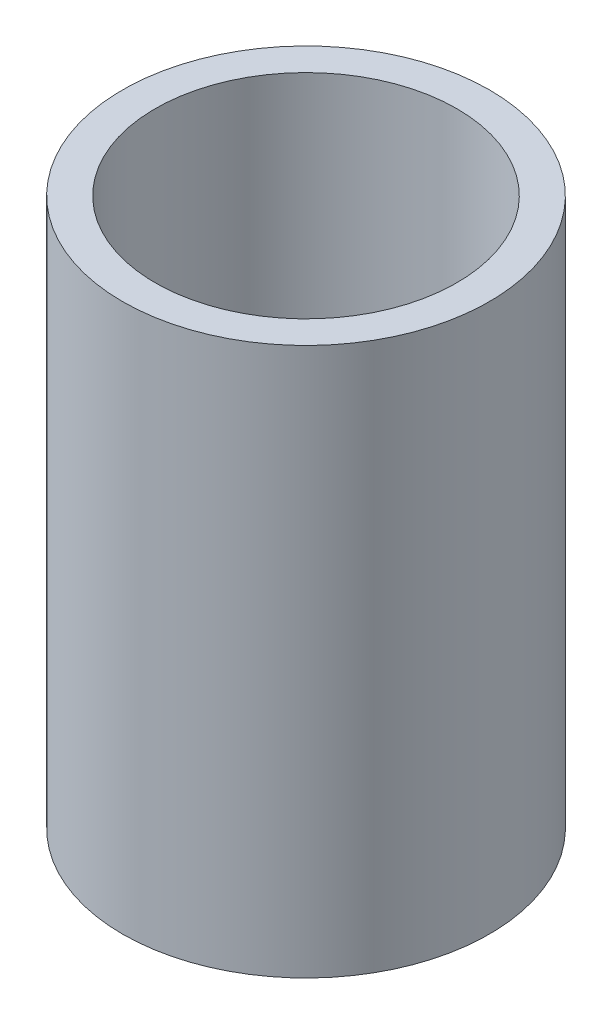
SolidWorks part; units mm, degrees
ref_plane "Front Plane" through (0, 0, 0) normal (0, 0, 1) x (1, 0, 0)
ref_plane "Top Plane" through (0, 0, 0) normal (0, 1, 0) x (1, 0, 0)
ref_plane "Right Plane" through (0, 0, 0) normal (1, 0, 0) x (0, 0, -1)
sketch "Sketch1" plane through (0, 0, 0) normal (0, 1, 0) x (1, 0, 0)
  circle A0 centre (0, 0) radius 37.5
  dimension "SLEEVE_OD" = 75
extrude "Boss-Extrude1" add sketch "Sketch1" along normal blind 112.0046
sketch "Sketch2" plane through (0, 0, 0) normal (0, 1, 0) x (1, 0, 0)
  circle A0 centre (0, 0) radius 30.8412
  dimension "BORE_D" = 61.6824
extrude "Cut-Extrude1" cut sketch "Sketch2" along normal through all
chamfer "Chamfer1" distance 3.4538 angle 60 rebuild error yes
